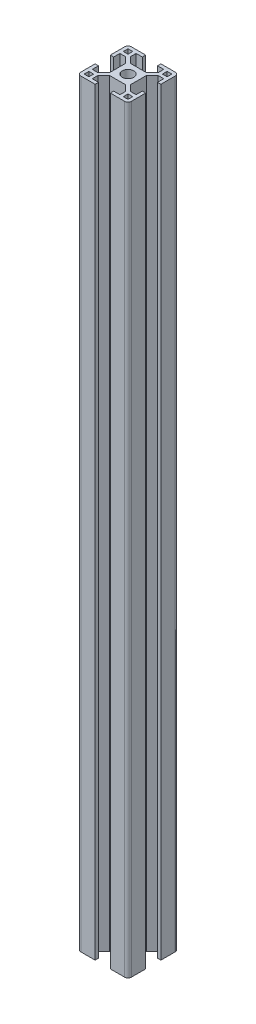
SolidWorks part; units mm, degrees
ref_plane "Front plane" through (0, 0, 0) normal (0, 0, 1) x (1, 0, 0)
ref_plane "Top plane" through (0, 0, 0) normal (0, 1, 0) x (1, 0, 0)
ref_plane "Right plane" through (0, 0, 0) normal (1, 0, 0) x (0, 0, -1)
ref_axis "Axis X" through (0, 0, 0) along (1, 0, 0)
ref_axis "Axis Y" through (0, 0, 0) along (0, 1, 0)
ref_axis "Axis Z" through (0, 0, 0) along (0, 0, 1)
sketch "Sketch1" plane through (0, 0, 0) normal (0, 1, 0) x (1, 0, 0)
  line L1 (-10, 10) -> (10, 10)
  line L2 (-10, 10) -> (-10, -10)
  line L3 (-10, -10) -> (10, -10)
  line L4 (10, 10) -> (10, -10)
  line L5 (-10, 10) -> (10, -10) construction
  line L6 (-10, -10) -> (10, 10) construction
  point P0 (0, 0)
  dimension "D1" = 20
  dimension "D2" = 20
extrude "Extrude1" add sketch "Sketch1" along normal blind 300
sketch "Sketch2" plane through (0, 300, 0) normal (0, 1, 0) x (1, 0, 0)
  line L0 (0, 0) -> (10, 0) construction
  line L1 (10, -10) -> (10, 10) construction
  line L2 (10, 10) -> (-10, 10) construction
  line L3 (8.6667, 3) -> (11.3333, 3)
  line L4 (8.6667, 3) -> (8.6667, -3) construction
  line L5 (8.6667, -3) -> (11.3333, -3)
  line L6 (11.3333, 3) -> (11.3333, -3)
  line L7 (8.6667, 3) -> (11.3333, -3) construction
  line L8 (8.6667, -3) -> (11.3333, 3) construction
  line L9 (6.8, 8.6667) -> (8.6667, 8.6667)
  line L10 (6.8, 8.6667) -> (6.8, 6.8)
  line L11 (6.8, 6.8) -> (8.6667, 6.8)
  line L12 (8.6667, 8.6667) -> (8.6667, 6.8)
  line L13 (6.8, 8.6667) -> (8.6667, 6.8) construction
  line L14 (6.8, 6.8) -> (8.6667, 8.6667) construction
  line L15 (0, 0) -> (10, 10) construction
  line L16 (8.6667, 3) -> (8.6667, 5.4667)
  line L17 (8.6667, 5.4667) -> (6.4095, 5.4667)
  line L18 (6.4095, 5.4667) -> (4.1333, 3.1905)
  line L19 (4.1333, 3.1905) -> (4.1333, -3.1905)
  line L20 (4.1333, -3.1905) -> (6.4095, -5.4667)
  line L21 (6.4095, -5.4667) -> (8.6667, -5.4667)
  line L22 (8.6667, -5.4667) -> (8.6667, -3)
  line L65 (-3.1905, 4.1333) -> (-5.4667, 6.4095)
  line L66 (-5.4667, 6.4095) -> (-5.4667, 8.6667)
  line L67 (-5.4667, 8.6667) -> (-3, 8.6667)
  line L68 (3, 11.3333) -> (-3, 11.3333)
  line L69 (-3, 8.6667) -> (-3, 11.3333)
  line L70 (3, 8.6667) -> (3, 11.3333)
  line L71 (3, 8.6667) -> (5.4667, 8.6667)
  line L72 (5.4667, 8.6667) -> (5.4667, 6.4095)
  line L73 (5.4667, 6.4095) -> (3.1905, 4.1333)
  line L74 (3.1905, 4.1333) -> (-3.1905, 4.1333)
  line L75 (0, 10) -> (0, -10) construction
  line L76 (-10, -10) -> (10, -10) construction
  line L77 (0, 0) -> (-10, 0) construction
  line L78 (-10, 10) -> (-10, -10) construction
  line L79 (8.6667, -8.6667) -> (8.6667, -6.8)
  line L80 (6.8, -6.8) -> (8.6667, -6.8)
  line L81 (6.8, -8.6667) -> (6.8, -6.8)
  line L82 (6.8, -8.6667) -> (8.6667, -8.6667)
  line L83 (-6.8, 6.8) -> (-8.6667, 6.8)
  line L84 (-8.6667, 8.6667) -> (-8.6667, 6.8)
  line L85 (-6.8, 8.6667) -> (-8.6667, 8.6667)
  line L86 (-6.8, 8.6667) -> (-6.8, 6.8)
  line L87 (-6.8, -8.6667) -> (-8.6667, -8.6667)
  line L88 (-6.8, -8.6667) -> (-6.8, -6.8)
  line L89 (-6.8, -6.8) -> (-8.6667, -6.8)
  line L90 (-8.6667, -8.6667) -> (-8.6667, -6.8)
  line L91 (-6.4095, -5.4667) -> (-8.6667, -5.4667)
  line L92 (-4.1333, -3.1905) -> (-6.4095, -5.4667)
  line L93 (-4.1333, 3.1905) -> (-4.1333, -3.1905)
  line L94 (-6.4095, 5.4667) -> (-4.1333, 3.1905)
  line L95 (-8.6667, 5.4667) -> (-6.4095, 5.4667)
  line L96 (-8.6667, 3) -> (-8.6667, 5.4667)
  line L97 (-8.6667, 3) -> (-11.3333, 3)
  line L98 (-11.3333, 3) -> (-11.3333, -3)
  line L99 (-8.6667, -3) -> (-11.3333, -3)
  line L100 (-8.6667, -5.4667) -> (-8.6667, -3)
  line L101 (3.1905, -4.1333) -> (-3.1905, -4.1333)
  line L102 (5.4667, -6.4095) -> (3.1905, -4.1333)
  line L103 (5.4667, -8.6667) -> (5.4667, -6.4095)
  line L104 (3, -8.6667) -> (5.4667, -8.6667)
  line L105 (3, -8.6667) -> (3, -11.3333)
  line L106 (3, -11.3333) -> (-3, -11.3333)
  line L107 (-3, -8.6667) -> (-3, -11.3333)
  line L108 (-5.4667, -8.6667) -> (-3, -8.6667)
  line L109 (-5.4667, -6.4095) -> (-5.4667, -8.6667)
  line L110 (-3.1905, -4.1333) -> (-5.4667, -6.4095)
  circle A0 centre (0, 0) radius 2.2667
  point P9 (7.7333, 7.7333)
  point P20 (7.5381, 5.4667)
  point P27 (10, -3)
  point P34 (-3, 10)
  point P37 (5.4667, 7.5381)
  dimension "D10" = 4.5333
  dimension "D1" = 2.6667
  dimension "D2" = 6
  dimension "D3" = 1.3333
  dimension "D4" = 1.3333
  dimension "D5" = 4.5333
  dimension "D6" = 5.4667
  dimension "D7" = 0.6667
  dimension "D8" = 1.3333
extrude "Extrude2" cut sketch "Sketch2" against normal through all
fillet "Fillet1" radius 1.3333 4 edges at (10, 150, 10) (10, 150, -10) (-10, 150, 10) (-10, 150, -10)
equation "\"prof_width\"= 20'Aluminium profile parameters"
equation "\"D1@Sketch1\"=\"prof_width\""
equation "\"D2@Sketch1\"=\"prof_width\""
equation "\"prof_groove\"= 6"
equation "\"prof_length\"= 300"
equation "\"D1@Extrude1\"=\"prof_length\""
equation "\"D1@Sketch2\"=\"prof_width\"/30*4"
equation "\"D2@Sketch2\"=\"prof_groove\""
equation "\"D3@Sketch2\"=\"D1@Sketch2\"/2"
equation "\"D4@Sketch2\"=\"D3@Sketch2\""
equation "\"D5@Sketch2\"=\"prof_width\"/30*6.8"
equation "\"D6@Sketch2\"=\"prof_width\"/30*8.2"
equation "\"D7@Sketch2\"=\"D3@Sketch2\"/2"
equation "\"D8@Sketch2\"=\"D3@Sketch2\""
equation "\"D10@Sketch2\"=\"prof_width\"/30*6.8"
equation "\"D1@Fillet1\"=\"prof_width\"/30*2"
